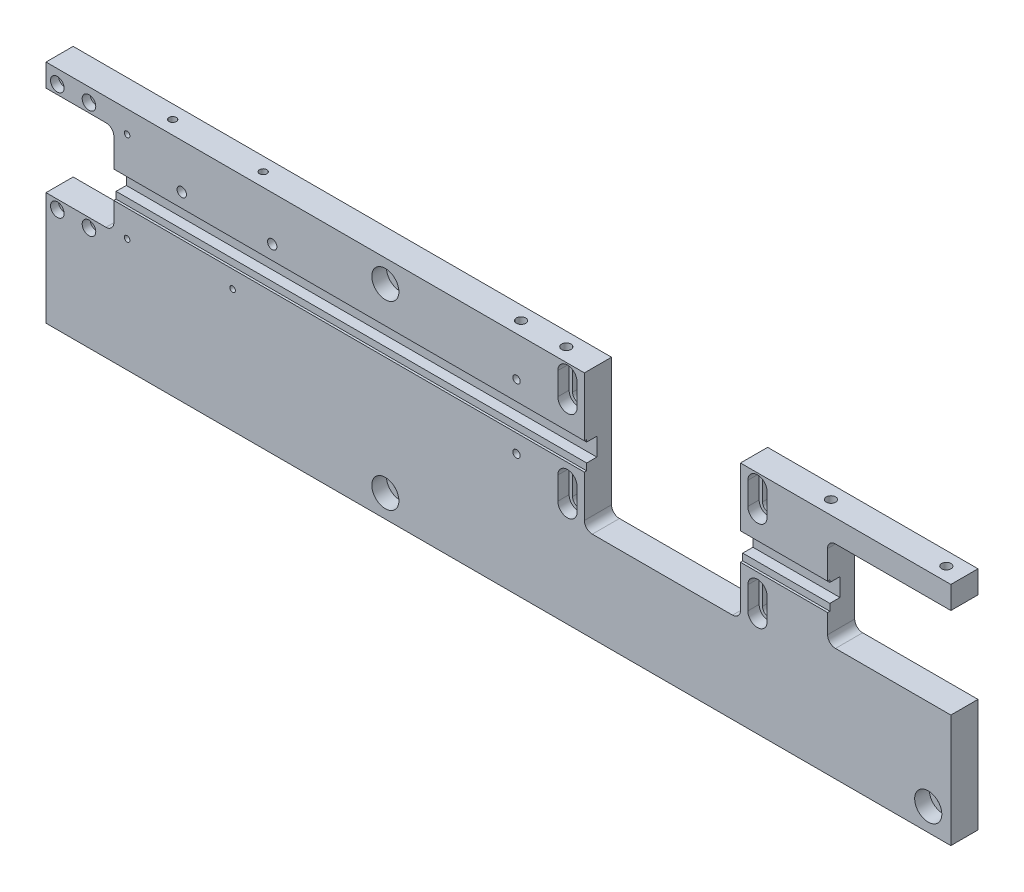
SolidWorks part; units mm, degrees
ref_plane "Front Plane" through (0, 0, 0) normal (0, 0, 1) x (1, 0, 0)
ref_plane "Top Plane" through (0, 0, 0) normal (0, 1, 0) x (1, 0, 0)
ref_plane "Right Plane" through (0, 0, 0) normal (1, 0, 0) x (0, 0, -1)
sketch "Sketch1" plane through (0, 0, 0) normal (0, 0, 1) x (1, 0, 0)
  line L1 (-200, -50) -> (200, -50)
  line L2 (-200, -50) -> (-200, 50)
  line L3 (-200, 50) -> (200, 50)
  line L4 (200, -50) -> (200, 50)
  line L5 (-200, -50) -> (200, 50) construction
  line L6 (-200, 50) -> (200, -50) construction
  point P0 (0, 0)
  dimension "D1" = 400
  dimension "D2" = 100
extrude "Base" add sketch "Sketch1" along normal blind 12
sketch "Sketch2" plane through (0, 0, 12) normal (0, 0, 1) x (1, 0, 0)
  line L0 (200, -50) -> (200, 50) construction
  line L1 (200, 0) -> (149, 0)
  line L2 (200, 0) -> (200, 40)
  line L3 (200, 40) -> (149, 40)
  line L4 (145.5, 3.5) -> (145.5, 36.5)
  line L5 (200, 50) -> (-200, 50) construction
  arc A0 (149, 0) -> (145.5, 3.5) centre (149, 3.5) cw
  arc A1 (149, 40) -> (145.5, 36.5) centre (149, 36.5) ccw
  dimension "D1" = 3.5
  dimension "D2" = 3.5
  dimension "D3" = 40
  dimension "D4" = 51
  dimension "D5" = 33
  dimension "D6" = 10
extrude "Part Tape Mover Cutout" cut sketch "Sketch2" against normal through all
sketch "Sketch3" plane through (0, 0, 12) normal (0, 0, 1) x (1, 0, 0)
  line L0 (200, 50) -> (-200, 50) construction
  line L1 (41.5, -10) -> (103.5, -10)
  line L2 (38, -6.5) -> (38, 50)
  line L3 (38, 50) -> (107, 50)
  line L4 (107, -6.5) -> (107, 50)
  line L5 (-200, -50) -> (200, -50) construction
  line L6 (200, -50) -> (200, 0) construction
  arc A0 (103.5, -10) -> (107, -6.5) centre (103.5, -6.5) ccw
  arc A1 (41.5, -10) -> (38, -6.5) centre (41.5, -6.5) cw
  point P9 (107, -10)
  point P12 (38, -10)
  dimension "D3" = 3.5
  dimension "D4" = 3.5
  dimension "D1" = 69
  dimension "D2" = 60
  dimension "D5" = 40
  dimension "D6" = 93
extrude "Press Plate Cutout" cut sketch "Sketch3" against normal through all
sketch "Sketch4" plane through (0, 0, 12) normal (0, 0, 1) x (1, 0, 0)
  line L0 (-200, 50) -> (-200, -50) construction
  line L1 (-200, 40) -> (-173.5, 40)
  line L2 (-200, 40) -> (-200, 0)
  line L3 (-200, 0) -> (-173.5, 0)
  line L4 (-170, 36.5) -> (-170, 3.5)
  line L5 (38, 50) -> (-200, 50) construction
  arc A0 (-173.5, 0) -> (-170, 3.5) centre (-173.5, 3.5) ccw
  arc A1 (-173.5, 40) -> (-170, 36.5) centre (-173.5, 36.5) cw
  dimension "D1" = 3.5
  dimension "D2" = 3.5
  dimension "D3" = 40
  dimension "D4" = 10
  dimension "D5" = 26.5
extrude "Roller Cutout" cut sketch "Sketch4" against normal through all
sketch "Sketch5" plane through (0, 0, 12) normal (0, 0, 1) x (1, 0, 0)
  line L0 (-170, 3.5) -> (-170, 36.5) construction
  line L1 (-170, 23) -> (145.5, 23)
  line L2 (-170, 23) -> (-170, 15)
  line L3 (-170, 15) -> (145.5, 15)
  line L4 (145.5, 23) -> (145.5, 15)
  line L5 (145.5, 36.5) -> (145.5, 3.5) construction
  line L6 (38, 50) -> (-200, 50) construction
  dimension "D1" = 8
  dimension "D2" = 27
extrude "Part Tape Cutout" cut sketch "Sketch5" against normal blind 5.5
sketch "Sketch6" plane through (0, 0, 12) normal (0, 0, 1) x (1, 0, 0)
  line L1 (-170, 24) -> (145.5, 24)
  line L2 (-170, 24) -> (-170, 12)
  line L3 (-170, 12) -> (145.5, 12)
  line L4 (145.5, 24) -> (145.5, 12)
  line L8 (-170, 3.5) -> (-170, 15) construction
  line L10 (-170, 15) -> (38, 15) construction
  line L11 (145.5, 15) -> (145.5, 3.5) construction
  dimension "D1" = 12
  dimension "D2" = 3
extrude "Cut-Extrude5" cut sketch "Sketch6" against normal blind 1
sketch "Sketch7" plane through (0, 0, 12) normal (0, 0, 1) x (1, 0, 0)
  line L0 (-200, -50) -> (200, -50) construction
  line L1 (200, -50) -> (200, 0) construction
  circle A0 centre (190, -40) radius 6
  circle A1 centre (-50, -40) radius 6
  circle A2 centre (-50, 40) radius 6
  dimension "D1" = 12
  dimension "D2" = 10
  dimension "D3" = 10
  dimension "D4" = 240
  dimension "D5" = 80
extrude "Cut-Extrude6" cut sketch "Sketch7" against normal blind 6.5
sketch "Sketch8" plane through (0, 0, 5.5) normal (0, 0, 1) x (1, 0, 0)
  circle A0 centre (190, -40) radius 3.25
  circle A1 centre (-50, -40) radius 3.25
  circle A2 centre (-50, 40) radius 3.25
  dimension "D1" = 6.5
extrude "Cut-Extrude7" cut sketch "Sketch8" against normal through all
sketch "Sketch9" plane through (0, 50, 0) normal (0, 1, 0) x (1, 0, 0)
  line L1 (200, -12) -> (200, 0) construction
  circle A0 centre (141, -6) radius 2.065
  circle A1 centre (192, -6) radius 2.065
  point P6 (200, -6)
  point P7 (0, 0)
  dimension "D1" = 4.13
  dimension "D2" = 51
  dimension "D3" = 8
extrude "Cut-Extrude8" cut sketch "Sketch9" against normal blind 10
sketch "Sketch11" plane through (0, 0, 12) normal (0, 0, 1) x (1, 0, 0)
  line L0 (114.5, 35) -> (114.5, 45) construction
  line L1 (110.25, 35) -> (110.25, 45)
  line L2 (118.75, 35) -> (118.75, 45)
  line L4 (107, 24) -> (107, 50) construction
  line L5 (200, 50) -> (107, 50) construction
  arc A0 (110.25, 35) -> (118.75, 35) centre (114.5, 35) ccw
  arc A1 (118.75, 45) -> (110.25, 45) centre (114.5, 45) ccw
  point P2 (114.5, 40)
  point P7 (32.6492, -5.5364)
  point P8 (26.8074, 1.2498)
  point P9 (114.4336, 37)
  point P11 (30.5, 31.428)
  dimension "D1" = 4.25
  dimension "D4" = 5
  dimension "D2" = 10
  dimension "D3" = 3.25
extrude "Cut-Extrude9" cut sketch "Sketch11" against normal blind 5
sketch "Sketch12" plane through (0, 0, 7) normal (0, 0, 1) x (1, 0, 0)
  line L4 (117.25, 35) -> (117.25, 45)
  line L5 (111.75, 45) -> (111.75, 35)
  line L6 (117.25, 35) -> (117.25, 45)
  line L7 (111.75, 45) -> (111.75, 35)
  arc A4 (111.75, 35) -> (117.25, 35) centre (114.5, 35) ccw
  arc A5 (117.25, 45) -> (111.75, 45) centre (114.5, 45) ccw
  arc A6 (111.75, 35) -> (117.25, 35) centre (114.5, 35) ccw
  arc A7 (117.25, 45) -> (111.75, 45) centre (114.5, 45) ccw
  dimension "D1" = 1.5
extrude "Cut-Extrude10" cut sketch "Sketch12" against normal through all
pattern_linear "LPattern1" count 2 spacing 84 along (-1, 0, 0) count 2 spacing 40 along (0, -1, 0) of "Cut-Extrude9", "Cut-Extrude10"
sketch "Sketch13" plane through (0, 0, 12) normal (0, 0, 1) x (1, 0, 0)
  line L0 (-173.5, 40) -> (-200, 40) construction
  line L1 (-200, 50) -> (-200, 40) construction
  circle A0 centre (-181, 44) radius 3
  circle A1 centre (-195, 44) radius 3
  point P8 (0, 0)
  point P9 (0, 0)
  dimension "D1" = 6
  dimension "D3" = 5
  dimension "D2" = 14
  dimension "D4" = 4
extrude "Cut-Extrude11" cut sketch "Sketch13" against normal blind 3.5
sketch "Sketch14" plane through (0, 0, 8.5) normal (0, 0, 1) x (1, 0, 0)
  circle A0 centre (-181, 44) radius 1.5
  circle A1 centre (-195, 44) radius 1.5
  dimension "D1" = 3
extrude "Cut-Extrude12" cut sketch "Sketch14" against normal through all
pattern_linear "LPattern2" count 2 spacing 48 along (0, -1, 0) of "Cut-Extrude11", "Cut-Extrude12"
sketch "Sketch15" plane through (0, 0, 12) normal (0, 0, 1) x (1, 0, 0)
  line L0 (38, 24) -> (-170, 24) construction
  line L1 (-170, 12) -> (38, 12) construction
  line L2 (-170, 24) -> (-170, 36.5) construction
  line L3 (-170, 3.5) -> (-170, 12) construction
  circle A0 centre (-164.15, 40.25) radius 1.23
  circle A1 centre (-164.15, 0.25) radius 1.23
  circle A2 centre (-117.5, 4.3) radius 1.23
  dimension "D2" = 2.46
  dimension "D3" = 5.85
  dimension "D5" = 7.7
  dimension "D1" = 16.25
  dimension "D4" = 40
  dimension "D6" = 52.5
extrude "Cut-Extrude13" cut sketch "Sketch15" against normal through all
sketch "Sketch16" plane through (0, 0, 12) normal (0, 0, 1) x (1, 0, 0)
  line L0 (38, 24) -> (-170, 24) construction
  line L1 (-170, 24) -> (-170, 36.5) construction
  circle A0 centre (-140, 30.25) radius 2.065
  circle A1 centre (-100, 30.25) radius 2.065
  point P4 (0, 0)
  point P7 (0, 0)
  dimension "D1" = 4.13
  dimension "D2" = 40
  dimension "D3" = 6.25
  dimension "D4" = 30
extrude "Cut-Extrude14" cut sketch "Sketch16" against normal through all
sketch "Sketch18" plane through (0, 0, 12) normal (0, 0, 1) x (1, 0, 0)
  line L0 (38, 50) -> (-200, 50) construction
  line L1 (38, 50) -> (38, 24) construction
  circle A0 centre (8, 32.5) radius 1.62
  circle A1 centre (8, 4) radius 1.62
  point P8 (0, 0)
  dimension "D1" = 3.24
  dimension "D3" = 17.5
  dimension "D4" = 30
  dimension "D2" = 28.5
extrude "Cut-Extrude15" cut sketch "Sketch18" against normal through all
sketch "Sketch19" plane through (0, 50, 0) normal (0, 1, 0) x (1, 0, 0)
  line L2 (38, 0) -> (38, -12) construction
  line L3 (-200, -12) -> (-200, 0) construction
  circle A0 centre (24, -6) radius 2.065
  circle A1 centre (4, -6) radius 2.065
  circle A2 centre (-110, -6) radius 1.62
  circle A3 centre (-150, -6) radius 1.62
  point P8 (-174.7327, -7.2376)
  point P9 (0, 0)
  point P10 (-200, -12)
  point P11 (-170, -12)
  point P14 (38, -6)
  dimension "D1" = 4.13
  dimension "D2" = 20
  dimension "D3" = 14
  dimension "D4" = 3.24
  dimension "D5" = 40
  dimension "D6" = 50
extrude "Cut-Extrude16" cut sketch "Sketch19" against normal blind 8
